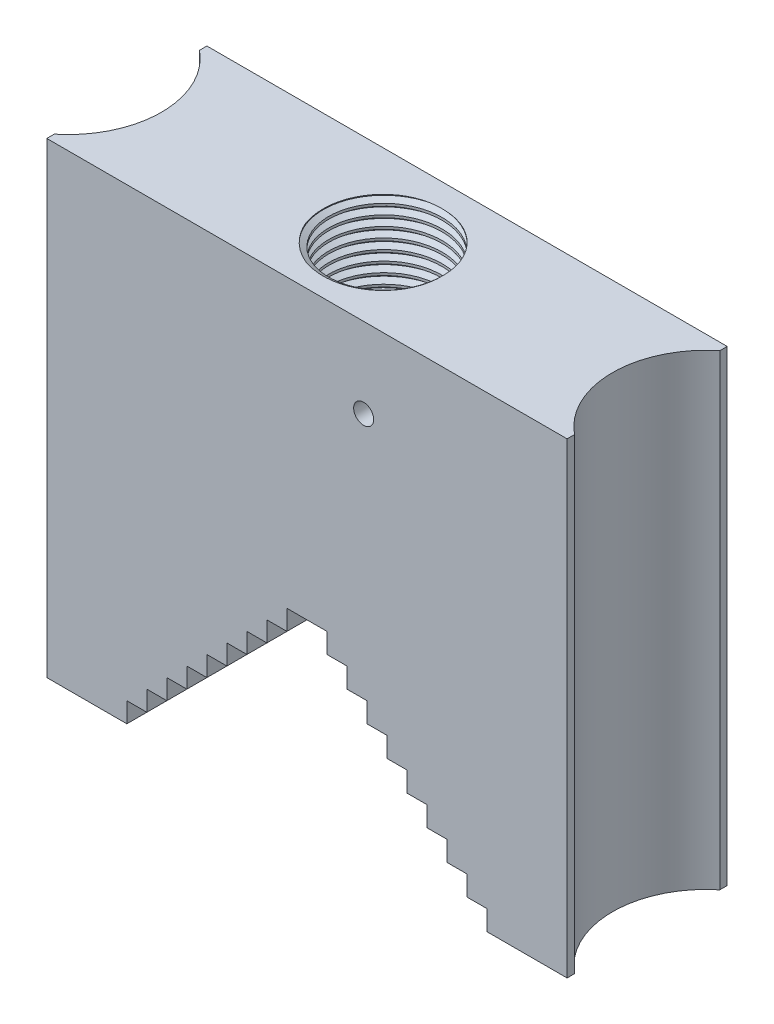
SolidWorks part; units mm, degrees
note: The reader was unsure of these and kept them because the rebuilt part matched: shared geometry of "Sketch1<3>".
ref_plane "Front Plane" through (0, 0, 0) normal (0, 0, 1) x (1, 0, 0)
ref_plane "Top Plane" through (0, 0, 0) normal (0, 1, 0) x (1, 0, 0)
ref_plane "Right Plane" through (0, 0, 0) normal (1, 0, 0) x (0, 0, -1)
sketch "Sketch1" plane through (0, 0, 0) normal (0, 1, 0) x (1, 0, 0)
  line L0 (0, 0) -> (0, -12) construction
  line L1 (-39, 12) -> (39, 12)
  line L2 (-39, 12) -> (-39, 10.8885)
  line L3 (-39, -12) -> (39, -12)
  line L4 (39, 12) -> (39, 10.8885)
  line L5 (-39, 12) -> (39, -12) construction
  line L6 (-39, -12) -> (39, 12) construction
  line L7 (-39, -10.8885) -> (-39, -12)
  line L8 (39, -10.8885) -> (39, -12)
  arc A0 (-39, -10.8885) -> (-39, 10.8885) centre (-47.8, 0) ccw
  arc A1 (39, -10.8885) -> (39, 10.8885) centre (47.8, 0) cw
  circle A2 centre (0, 0) radius 8.5
  point P0 (0, 0)
  dimension "D3" = 28
  dimension "D5" = 17
  dimension "D1" = 24
  dimension "D2" = 78
  dimension "D4" = 47.8
  dimension "D6" = 47.8
extrude "Boss-Extrude1" add sketch "Sketch1" against normal blind 70 contours L8 A1 L4 L1 L2 A0 L7 L3 A2 | A2
extrude "Cut-Extrude1" cut sketch "Sketch1<3>" against normal blind 24 contours A2
sketch "Sketch1<3>" plane through (0, 0, 0) normal (0, 1, 0) x (1, 0, 0) same geometry as "Sketch1"
sketch "Sketch2" plane through (0, 0, 12) normal (0, 0, 1) x (1, 0, 0)
  line L0 (0, 0) -> (0, -73.9364) construction
  line L1 (-27, -70) -> (-27, -67)
  line L2 (-39, -70) -> (39, -70) construction
  line L3 (-27, -67) -> (-24, -67)
  line L4 (-24, -67) -> (-24, -64)
  line L5 (-24, -64) -> (-21, -64)
  line L6 (-21, -64) -> (-21, -61)
  line L7 (0, -43) -> (-27, -70) construction
  line L8 (-21, -61) -> (-18, -61)
  line L9 (-18, -61) -> (-18, -58)
  line L10 (-18, -58) -> (-15, -58)
  line L11 (-15, -58) -> (-15, -55)
  line L12 (-15, -55) -> (-12, -55)
  line L13 (-12, -55) -> (-12, -52)
  line L14 (-12, -52) -> (-9, -52)
  line L15 (-9, -52) -> (-9, -49)
  line L16 (-9, -49) -> (-6, -49)
  line L17 (-6, -49) -> (-6, -46)
  line L18 (-6, -46) -> (-3, -46)
  line L19 (-3, -46) -> (-3, -43)
  line L20 (-3, -43) -> (3, -43)
  line L21 (3, -46) -> (3, -43)
  line L22 (6, -46) -> (3, -46)
  line L23 (6, -49) -> (6, -46)
  line L24 (9, -49) -> (6, -49)
  line L25 (9, -52) -> (9, -49)
  line L26 (12, -52) -> (9, -52)
  line L27 (12, -55) -> (12, -52)
  line L28 (15, -55) -> (12, -55)
  line L29 (15, -58) -> (15, -55)
  line L30 (18, -58) -> (15, -58)
  line L31 (18, -61) -> (18, -58)
  line L32 (21, -61) -> (18, -61)
  line L33 (21, -64) -> (21, -61)
  line L34 (24, -64) -> (21, -64)
  line L35 (24, -67) -> (24, -64)
  line L36 (27, -67) -> (24, -67)
  line L37 (27, -70) -> (27, -67)
  line L38 (-39, 0) -> (39, 0) construction
  line L39 (39, -70) -> (39, 0) construction
  circle A0 centre (8.5, -12) radius 1.5
  point P26 (0, -43)
  point P49 (0, 0)
  dimension "D14" = 3
  dimension "D1" = 27
  dimension "D2" = 3
  dimension "D3" = 3
  dimension "D4" = 3
  dimension "D5" = 3
  dimension "D6" = 3
  dimension "D7" = 3
  dimension "D8" = 3
  dimension "D9" = 3
  dimension "D10" = 3
  dimension "D11" = 3
  dimension "D12" = 3
  dimension "D13" = 3
  dimension "D15" = 12
  dimension "D16" = 30.5
extrude "Cut-Extrude2" cut sketch "Sketch2" against normal blind 40 and the other way through all contours L16 L37 L36 L35 L34 L33 L32 L31 L30 L29 L28 L27 L26 L25 L24 L23 L22 L21 L20 L19 L18 L17 L15 L14 L13 L12 L11 L10 L9 L8 L6 L5 L4 L3 L1 | A0
thread "Thread1" pitch 1.5 start angle 0, offset 0, length 25, pitch 1.5, diameter 17
ref_plane "Plane1" through (8.5, -24, 0) normal (0, 0, 1) x (1, 0, 0)
sketch "Thread Profile1" plane through (8.5, -24, 0) normal (0, 0, 1) x (1, 0, 0)
  line L0 (0, 0) -> (0, 1.5) construction
  line L1 (0, 0) -> (0.8119, 0.4687)
  line L2 (0.8119, 0.4687) -> (0.8119, 0.6562)
  line L3 (0.8119, 0.6562) -> (0, 1.125)
  line L4 (0.8119, 0.5625) -> (0, 0.5625) construction
  line L11 (0, 0) -> (0, 1.125)
  point P2 (0, 0)
  dimension "Pitch" = 1.5
  dimension "Profile_Angle" = 60
  dimension "Profile_Land" = 0.1875
  dimension "Profile_Height" = 0.8119
